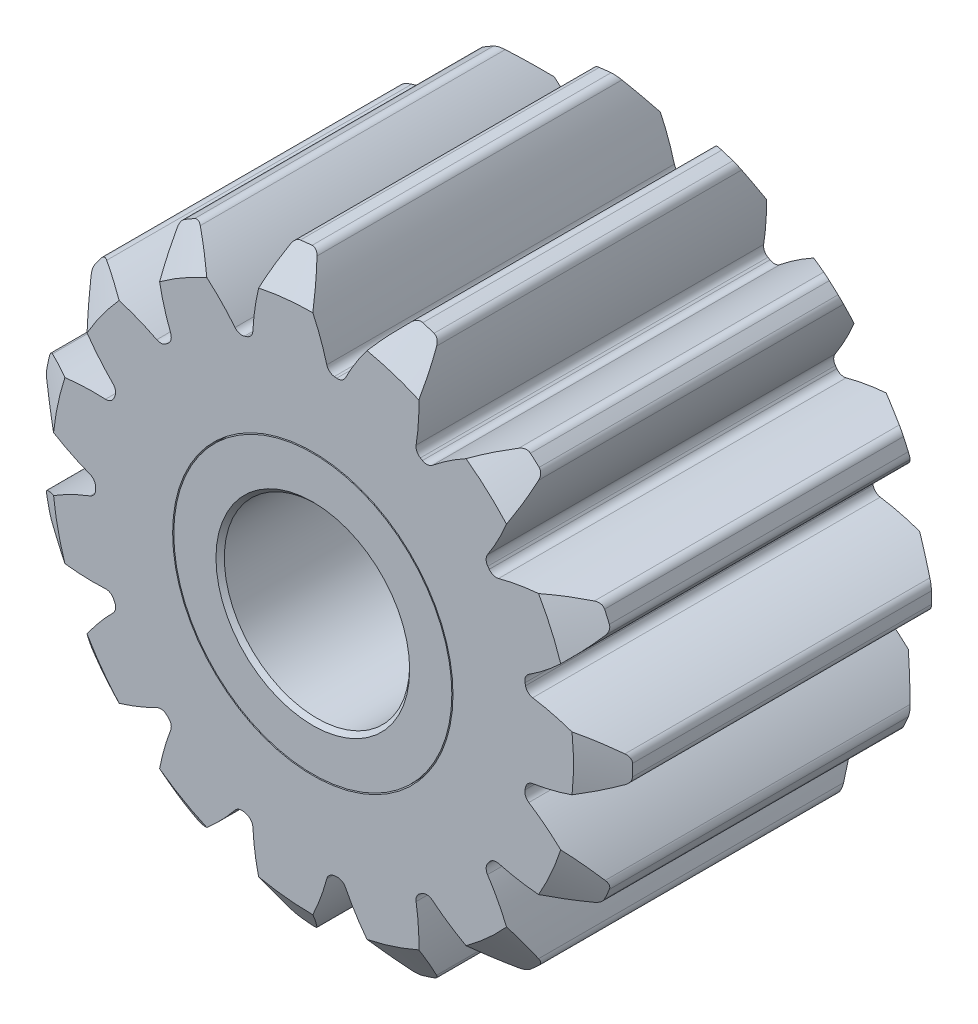
SolidWorks part; units mm, degrees
ref_plane "前视基准面" through (0, 0, 0) normal (0, 0, 1) x (1, 0, 0)
ref_plane "上视基准面" through (0, 0, 0) normal (0, 1, 0) x (1, 0, 0)
ref_plane "右视基准面" through (0, 0, 0) normal (1, 0, 0) x (0, 0, -1)
sketch "草图1" plane through (0, 0, 0) normal (1, 0, 0) x (0, 0, -1)
  line L0 (0, 0) -> (15, 0) construction
  line L1 (0, 4) -> (15, 4)
  line L4 (15, 4) -> (15, 12.75)
  line L5 (15, 12.75) -> (0, 12.75)
  line L6 (0, 12.75) -> (0, 4)
  line L7 (0, 0) -> (-1.5, 0) construction
  line L8 (-1.5, 0) -> (-1.5, -15) construction
  dimension "P" = 8
  dimension "B" = 15
  dimension "M" = 1.5
  dimension "Z" = 15
  dimension "D" = 25.5
sketch "草图2" plane through (0, 0, 0) normal (0, 0, 1) x (1, 0, 0)
  line L0 (0, 4) -> (0, 8) construction
  circle A0 centre (0, 0) radius 4
  circle A3 centre (0, 0) radius 6
  point P6 (0, 6)
  dimension "(D1)" = 4
sketch "草图11" plane through (-11.8785, -4, 0) normal (0, 0, 1) x (1, 0, 0)
  line L0 (11.8785, 4) -> (24.6285, 4) construction
  line L1 (23.0669, 2.8241) -> (11.8785, 4) construction
  circle A0 centre (11.8785, 4) radius 9.375
  arc A1 (21.1088, 2.3592) -> (21.2535, 4) centre (11.8785, 4) ccw construction
  arc A2 (23.0669, 2.8241) -> (23.1285, 4) centre (11.8785, 4) ccw construction
  arc A3 (24.6198, 3.5289) -> (24.6198, 4.4711) centre (11.8785, 4) ccw construction
  arc A4 (21.1088, 2.3592) -> (24.6198, 3.5289) centre (19.8709, 11.9289) ccw construction
  point P1 (26.8785, 4)
  point P7 (11.8785, 5.5)
  point P13 (23.0669, 2.8241)
  point P17 (24.6198, 4.4711)
  point P18 (21.1088, 5.6408)
  dimension "D1" = 25.5
  dimension "D" = 22.5
  dimension "D2" = 18.75
  dimension "m" = 1.5
  dimension "z" = 15
  dimension "D3" = 6
  dimension "D4" = 0.9425
  dimension "D5" = 3.2987
extrude "拉伸-齿轮a" add sketch "草图11" against normal blind 15
sketch "草图3" plane through (-1.3611, -4, 0) normal (0, 0, 1) x (1, 0, 0)
  line L1 (1.3611, 4) -> (14.1111, 4) construction
  line L2 (10.7361, 4) -> (14.1111, 4) construction
  circle A2 centre (1.3611, 4) radius 9.375 construction
  arc A3 (10.5914, 2.3592) -> (14.1024, 3.5289) centre (9.3535, 11.9289) ccw construction
  arc A4 (14.1024, 3.5289) -> (14.1024, 4.4711) centre (1.3611, 4) ccw construction
  arc A5 (10.5914, 2.3592) -> (10.5914, 5.6408) centre (1.3611, 4) ccw
  arc A6 (10.5914, 2.3592) -> (14.1024, 3.5289) centre (9.3535, 11.9289) ccw
  arc A7 (14.1024, 3.5289) -> (14.1024, 4.4711) centre (1.3611, 4) ccw
  arc A8 (10.5914, 5.6408) -> (14.1024, 4.4711) centre (9.3535, -3.9289) cw
extrude "拉伸-齿轮b" add sketch "草图3" along normal up to surface (-15 mm away) up to face at (9.375, 0, -15)
fillet "圆角-齿轮" radius 0.375 4 edges at (12.7413, -0.4711, -7.5) (12.7413, 0.4711, -7.5) (9.2303, -1.6408, -7.5) (9.2303, 1.6408, -7.5)
pattern_circular "阵列-齿轮" count 15 over 360 about axis through (0, 0, -15) along (0, 0, 1) of "拉伸-齿轮b", "圆角-齿轮"
sketch "草图4" plane through (0, 0, -15) normal (0, 0, -1) x (-1, 0, 0)
  line L0 (-11.25, 0) -> (-14.25, 0) construction
  circle A0 centre (0, 0) radius 14.25
  circle A1 centre (0, 0) radius 11.25
extrude "切除-齿轮" cut sketch "草图4" against normal blind 1.5 draft 55
extrude "切除-拉伸2" cut sketch "草图4<2>" along normal blind 1.5 draft 55 from vertex starting at point (0, 4, 0)
sketch "草图4<2>" plane through (0, 0, -15) normal (0, 0, -1) x (-1, 0, 0) same geometry as "草图4"
sketch "草图13" plane through (0, 0, 0) normal (0, 0, 1) x (1, 0, 0)
  circle A0 centre (0, 0) radius 4
extrude "切除-拉伸4" cut sketch "草图13" against normal through all
chamfer "倒角1" distance 0.18 angle 45 2 edges at (4, 0, -15) (4, 0, 0)
sketch "草图14" plane through (0, 0, 0) normal (1, 0, 0) x (0, 0, -1)
  line L0 (0, 0) -> (15, 0) construction
  line L1 (0, 6) -> (0, -6) construction
  line L2 (18.75, 6.05) -> (11.25, 6.05)
  line L3 (18.75, 6.05) -> (18.75, 6)
  line L4 (18.75, 6) -> (11.25, 6)
  line L5 (11.25, 6.05) -> (11.25, 6)
  line L6 (3.75, 6.05) -> (-3.75, 6.05)
  line L7 (3.75, 6.05) -> (3.75, 6)
  line L8 (3.75, 6) -> (-3.75, 6)
  line L9 (-3.75, 6.05) -> (-3.75, 6)
  line L10 (15, 4) -> (15, 12.75) construction
  line L11 (11.25, 6) -> (3.75, 6) construction
  point P12 (0, 6)
  point P16 (15, 6)
  dimension "D1" = 0.05
revolve "金属" cut sketch "草图14" angle 360 mid plane about L0
